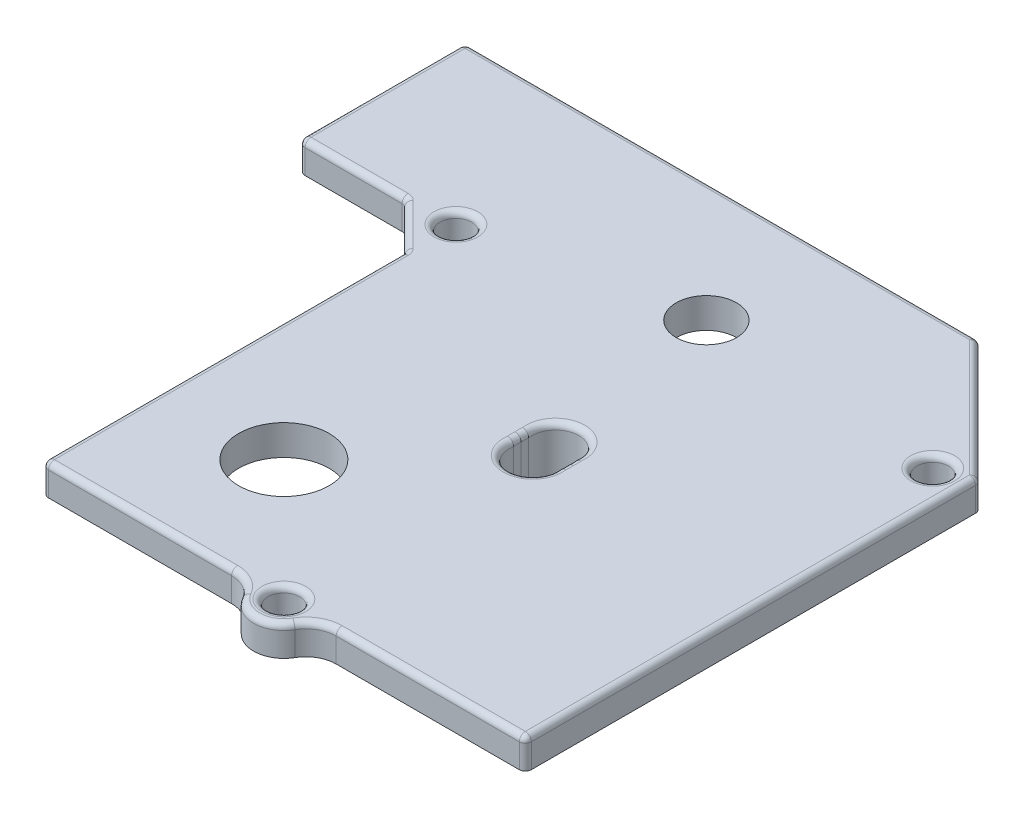
SolidWorks part; units mm, degrees
ref_plane "前视基准面" through (0, 0, 0) normal (0, 0, 1) x (1, 0, 0)
ref_plane "上视基准面" through (0, 0, 0) normal (0, 1, 0) x (1, 0, 0)
ref_plane "右视基准面" through (0, 0, 0) normal (1, 0, 0) x (0, 0, -1)
other "Configuration Table"
sketch "草图1" plane through (0, 0, 0) normal (0, 1, 0) x (1, 0, 0)
  line L0 (0.7016, -0.1135) -> (0.7016, 23.8865)
  line L5 (0.7016, 23.8865) -> (-2.2984, 26.8865)
  line L6 (-2.2984, 26.8865) -> (-9.2984, 26.8865)
  line L7 (-9.2984, 26.8865) -> (-9.2984, 37.8865)
  line L8 (-9.2984, 37.8865) -> (24.7016, 37.8865)
  line L9 (24.7016, 37.8865) -> (32.7016, 29.8865)
  line L10 (32.7016, 29.8865) -> (32.7016, -0.1135)
  line L11 (32.7016, -0.1135) -> (0.7016, -0.1135)
extrude "凸台-拉伸1" add sketch "草图1" along normal blind 2
sketch "草图2" plane through (0, 0, 0) normal (0, -1, 0) x (1, 0, 0)
  line L16 (32.7016, 0.1135) -> (0.7016, 0.1135)
  line L17 (0.7016, 0.1135) -> (0.7016, -23.8865)
  line L18 (0.7016, -23.8865) -> (-2.2984, -26.8865)
  line L19 (-2.2984, -26.8865) -> (-9.2984, -26.8865)
  line L20 (-9.2984, -26.8865) -> (-9.2984, -37.8865)
  line L21 (-9.2984, -37.8865) -> (24.7016, -37.8865)
  line L22 (24.7016, -37.8865) -> (32.7016, -29.8865)
  line L23 (32.7016, -29.8865) -> (32.7016, 0.1135)
  line L24 (32.7016, 0.1135) -> (0.7016, 0.1135)
  line L25 (0.7016, 0.1135) -> (0.7016, -23.8865)
  line L26 (0.7016, -23.8865) -> (-2.2984, -26.8865)
  line L27 (-2.2984, -26.8865) -> (-9.2984, -26.8865)
  line L28 (-9.2984, -26.8865) -> (-9.2984, -37.8865)
  line L29 (-9.2984, -37.8865) -> (24.7016, -37.8865)
  line L30 (24.7016, -37.8865) -> (32.7016, -29.8865)
  line L31 (32.7016, -29.8865) -> (32.7016, 0.1135)
  arc A2 (18.2313, -16.6365) -> (15.1719, -16.6365) centre (16.7016, -16.3865) ccw
  arc A3 (15.1719, -16.6365) -> (15.1719, -17.1365) centre (16.7016, -16.8865) ccw
  arc A4 (15.1719, -17.1365) -> (15.1719, -17.6365) centre (16.7016, -17.3865) ccw
  arc A5 (18.2313, -17.1365) -> (18.2313, -16.6365) centre (16.7016, -16.8865) ccw
  arc A6 (18.2313, -17.6365) -> (18.2313, -17.1365) centre (16.7016, -17.3865) ccw
  arc A8 (15.1719, -17.6365) -> (18.2313, -17.6365) centre (16.7016, -17.8865) ccw
  circle A9 centre (16.7016, -17.1365) radius 3.5
  dimension "D2" = 7
  dimension "D1" = 0
extrude "凸台-拉伸2" add sketch "草图2" along normal blind 5.7 contours A9 A8 A4 A3 A2 A5 A6 region at (13.3006, 0, -17.1365)
sketch "草图3" plane through (0, 0, 0) normal (0, -1, 0) x (1, 0, 0)
  arc A9 (18.2313, -17.6365) -> (18.2313, -17.1365) centre (16.7016, -17.3865) ccw
  arc A10 (18.2313, -17.1365) -> (18.2313, -16.6365) centre (16.7016, -16.8865) ccw
  arc A11 (18.2313, -16.6365) -> (15.1719, -16.6365) centre (16.7016, -16.3865) ccw
  arc A12 (18.2313, -17.6365) -> (18.2313, -17.1365) centre (16.7016, -17.3865) ccw
  arc A13 (18.2313, -17.1365) -> (18.2313, -16.6365) centre (16.7016, -16.8865) ccw
  arc A14 (18.2313, -16.6365) -> (15.1719, -16.6365) centre (16.7016, -16.3865) ccw
  arc A24 (15.1719, -17.6365) -> (18.2313, -17.6365) centre (16.7016, -17.8865) ccw
  arc A25 (18.2313, -17.6365) -> (18.2313, -17.1365) centre (16.7016, -17.3865) ccw
  arc A26 (18.2313, -17.1365) -> (18.2313, -16.6365) centre (16.7016, -16.8865) ccw
  arc A27 (18.2313, -16.6365) -> (15.1719, -16.6365) centre (16.7016, -16.3865) ccw
  arc A28 (15.1719, -16.6365) -> (15.1719, -17.1365) centre (16.7016, -16.8865) ccw
  arc A29 (15.1719, -17.1365) -> (15.1719, -17.6365) centre (16.7016, -17.3865) ccw
  arc A30 (15.1719, -17.6365) -> (18.2313, -17.6365) centre (16.7016, -17.8865) ccw
  arc A31 (18.2313, -17.6365) -> (18.2313, -17.1365) centre (16.7016, -17.3865) ccw
  arc A32 (18.2313, -17.1365) -> (18.2313, -16.6365) centre (16.7016, -16.8865) ccw
  arc A33 (18.2313, -16.6365) -> (15.1719, -16.6365) centre (16.7016, -16.3865) ccw
  arc A34 (15.1719, -16.6365) -> (15.1719, -17.1365) centre (16.7016, -16.8865) ccw
  arc A35 (15.1719, -17.1365) -> (15.1719, -17.6365) centre (16.7016, -17.3865) ccw
  arc M10 (15.1719, -17.6365) -> (18.2313, -17.6365) centre (16.7016, -17.8865) ccw
  arc M11 (18.2313, -17.6365) -> (18.2313, -17.1365) centre (16.7016, -17.3865) ccw
  arc M12 (18.2313, -17.1365) -> (18.2313, -16.6365) centre (16.7016, -16.8865) ccw
  arc M13 (18.2313, -16.6365) -> (15.1719, -16.6365) centre (16.7016, -16.3865) ccw
  arc M14 (15.1719, -16.6365) -> (15.1719, -17.1365) centre (16.7016, -16.8865) ccw
  arc M15 (15.1719, -17.1365) -> (15.1719, -17.6365) centre (16.7016, -17.3865) ccw
  dimension "D1" = 0
  dimension "D2" = 0
extrude "切除-拉伸1" cut sketch "草图3" against normal blind 4.7 contours M15 M10 M11 M12 M13 M14 region at (16.7016, 0, -17.1365)
sketch "草图5" plane through (0, 0, 0) normal (0, -1, 0) x (1, 0, 0)
  circle A0 centre (30.7016, -28.8865) radius 1.05
  circle A1 centre (0.9016, -27.0865) radius 1.05
  dimension "D1" = 2.1
  dimension "D2" = 2.1
extrude "切除-拉伸2" cut sketch "草图5" against normal blind 10
sketch "草图6" plane through (0, 0, 0) normal (0, -1, 0) x (-1, 0, 0)
  line L0 (-0.7016, -0.1135) -> (-32.7016, -0.1135) construction
  circle A0 centre (-16.7016, -0.1135) radius 2
  dimension "D1" = 4
extrude "凸台-拉伸3" add sketch "草图6" against normal blind 2
fillet "圆角1" radius 2 2 edges at (18.7016, 1, 0.1135) (14.7016, 1, 0.1135)
sketch "草图7" plane through (0, 2, 0) normal (0, 1, 0) x (1, 0, 0)
  circle A0 centre (16.7016, -0.1135) radius 1.05
  dimension "D1" = 2.1
extrude "切除-拉伸3" cut sketch "草图7" against normal blind 2
fillet "圆角2" radius 0.4 8 edges at (24.7016, 1, -37.8865) (32.7016, 1, -29.8865) (32.7016, 1, 0.1135) (0.7016, 1, 0.1135) (0.7016, 1, -23.8865) (-2.2984, 1, -26.8865) (-9.2984, 1, -37.8865) (-9.2984, 1, -26.8865)
fillet "圆角3" radius 0.4 29 edges at (32.6712, 2, -29.8739) (32.7016, 2, -15.0037) (32.5845, 2, -0.0037) (26.2337, 2, 0.1135) (19.1657, 2, 0.3815) (16.7016, 2, 2.1135) (14.2375, 2, 0.3815) (7.1696, 2, 0.1135) (0.8188, 2, -0.0037) (0.7016, 2, -12.0037) (0.6712, 2, -23.8739) (-0.7984, 2, -25.3865) (-2.311, 2, -26.8561) (-5.6812, 2, -26.8865) (-9.1812, 2, -27.0037) (-9.2984, 2, -32.3865) (-9.1812, 2, -37.7693) (7.8188, 2, -37.8865) (24.689, 2, -37.8561) (28.7016, 2, -33.8865) (16.7016, 2, -14.8365) (18.2516, 2, -16.8865) (18.2516, 2, -17.3865) (16.7016, 2, -19.4365) (15.1516, 2, -17.3865) (15.1516, 2, -16.8865) (0.9016, 2, -28.1365) (30.7016, 2, -29.9365) (16.7016, 2, 1.1635)
chamfer "倒角1" distance 2 angle 45 1 edges at (16.7016, 0, -20.6365)
chamfer "倒角2" distance 0.4 angle 45 1 edges at (16.7016, -5.7, -20.6365)
sketch "草图8" plane through (0, 0, 0) normal (0, -1, 0) x (1, 0, 0)
  line L0 (0.7016, -23.7208) -> (0.7016, -0.2865) construction
  line L1 (1.1016, 0.1135) -> (13.2375, 0.1135) construction
  line L2 (24.5359, -37.8865) -> (-8.8984, -37.8865) construction
  line L3 (-9.2984, -37.4865) -> (-9.2984, -27.2865) construction
  circle A0 centre (8.7016, -7.8865) radius 3
  circle A1 centre (14.7016, -29.8865) radius 2
  dimension "D1" = 6
  dimension "D4" = 4
  dimension "D6" = 24
  dimension "D2" = 8
  dimension "D3" = 8
  dimension "D5" = 8
extrude "切除-拉伸5" cut sketch "草图8" against normal through all
